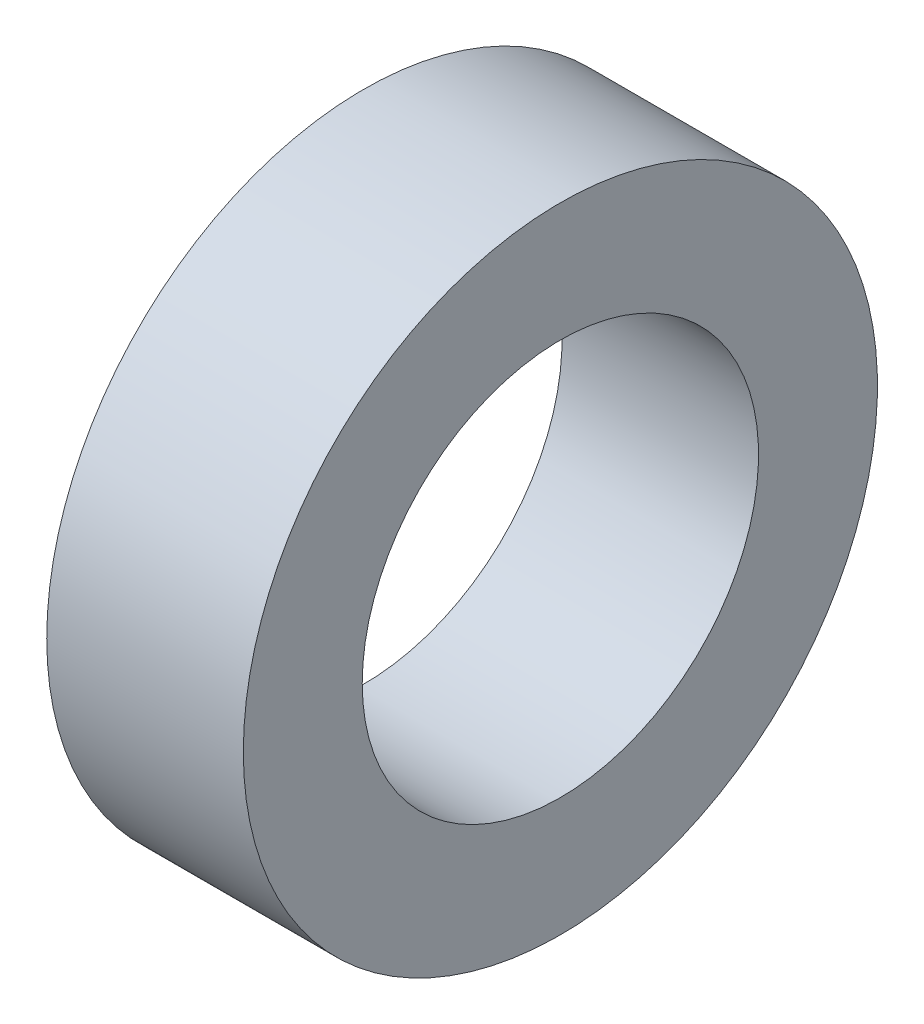
SolidWorks part; units mm, degrees
ref_plane "Front Plane" through (0, 0, 0) normal (0, 0, 1) x (1, 0, 0)
ref_plane "Top Plane" through (0, 0, 0) normal (0, 1, 0) x (1, 0, 0)
ref_plane "Right Plane" through (0, 0, 0) normal (1, 0, 0) x (0, 0, -1)
sketch "Sketch2" plane through (0, 0, 0) normal (0, 0, 1) x (1, 0, 0)
  line L0 (0, 0) -> (58.591, 0) construction
  line L2 (0, 0) -> (18.4, 0)
  line L3 (0, 0) -> (0, 2.5)
  line L4 (0, 2.5) -> (18.4, 2.5)
  line L5 (18.4, 0) -> (18.4, 2.5)
  line L6 (6, 2.5) -> (6, 6)
  line L11 (6, 6) -> (9.97, 6)
  line L16 (12.97, 6) -> (12.97, 3)
  line L17 (12.97, 3) -> (13.6304, 3)
  line L18 (13.6304, 3) -> (13.6304, 2.5)
  line L19 (13.6304, 2.5) -> (6, 2.5)
  line L22 (13.6304, 2.5) -> (16.1104, 2.5)
  line L23 (13.6304, 2.5) -> (13.6304, 4)
  line L24 (13.6304, 4) -> (16.1104, 4)
  line L25 (16.1104, 2.5) -> (16.1104, 4)
  line L27 (6, 6) -> (9.97, 6)
  line L28 (6, 6) -> (6, 9)
  line L29 (6, 9) -> (9.97, 9)
  line L30 (9.97, 6) -> (9.97, 9)
  line L31 (6, 9) -> (6, 8.25)
  line L32 (6, 8.25) -> (5, 8.25)
  line L33 (8.58, 22.001) -> (8.58, 12.476) construction
  line L34 (5, 12.476) -> (12.16, 12.476)
  line L35 (9.97, 9) -> (12.16, 9)
  line L36 (5, 7.5) -> (3, 7.5)
  line L37 (5, 8.25) -> (5, 12.476)
  line L38 (5, 7.5) -> (5, 14)
  line L39 (5, 14) -> (3, 14)
  line L40 (3, 7.5) -> (3, 14)
  line L41 (5, 22.001) -> (12.16, 22.001)
  line L42 (5, 22.001) -> (5, 30.1625)
  line L43 (5, 30.1625) -> (12.16, 30.1625)
  line L44 (12.16, 22.001) -> (12.16, 30.1625)
  line L49 (16.6304, 22.001) -> (16.6304, 7.5)
  line L51 (23.0104, 7.5) -> (23.0104, 6.5)
  line L54 (16.1104, 4) -> (13.6304, 4)
  line L56 (18.0304, 7.5) -> (23.0104, 7.5)
  line L57 (13.16, 22.001) -> (16.6304, 22.001)
  line L58 (16.1104, 3.5) -> (20.0104, 3.5)
  line L59 (29.9004, 14) -> (26.9004, 11)
  line L60 (4, 31.75) -> (18.0304, 31.75)
  line L61 (18.0304, 7.5) -> (23.0104, 7.5)
  line L62 (18.0304, 7.5) -> (18.0304, 12)
  line L63 (18.0304, 12) -> (23.0104, 12)
  line L64 (23.0104, 7.5) -> (23.0104, 12)
  line L65 (18.0304, 31.75) -> (18.0304, 12)
  line L66 (23.0104, 11) -> (26.9004, 11)
  line L67 (34.8004, 23) -> (31.3004, 19.5)
  line L68 (35.8004, 31) -> (38.7904, 33.99)
  line L69 (29.9004, 14) -> (29.9004, 15)
  line L70 (29.9004, 15) -> (22.9304, 15)
  line L71 (22.9304, 15) -> (21.0304, 15)
  line L72 (18.0304, 7.5) -> (16.6304, 7.5)
  line L73 (21.0304, 15) -> (21.0304, 43)
  line L74 (20.0304, 40) -> (10.0704, 40)
  line L75 (10.0704, 40) -> (4, 40)
  line L76 (21.0304, 43) -> (20.0304, 43)
  line L77 (22.9304, 15) -> (29.9004, 15)
  line L78 (22.9304, 15) -> (22.9304, 21)
  line L79 (22.9304, 21) -> (29.9004, 21)
  line L80 (29.9004, 15) -> (29.9004, 21)
  line L81 (10.0704, 40) -> (20.0304, 40)
  line L82 (10.0704, 40) -> (10.0704, 50)
  line L83 (10.0704, 50) -> (20.0304, 50)
  line L84 (20.0304, 40) -> (20.0304, 50)
  line L85 (4, 40) -> (4, 31.75)
  line L86 (12.97, 3) -> (12.97, 2.5)
  line L87 (31.3004, 19.5) -> (29.9004, 19.5)
  line L88 (21.51, 63.5) -> (21.51, 44)
  line L89 (21.51, 63.5) -> (25.9304, 63.5)
  line L90 (25.9304, 63.5) -> (25.9304, 25)
  line L91 (27.8304, 25) -> (25.9304, 25)
  line L92 (10.0704, 48) -> (9, 48)
  line L93 (9, 48) -> (9, 53.476)
  line L94 (9, 53.476) -> (20.0304, 53.476)
  line L95 (20.0304, 53.476) -> (20.0304, 50)
  line L96 (14.5152, 63.001) -> (14.5152, 53.476) construction
  line L97 (9, 63.001) -> (20.0304, 63.001)
  line L98 (9, 63.001) -> (9, 68.2625)
  line L99 (9, 68.2625) -> (20.0304, 68.2625)
  line L100 (20.0304, 63.001) -> (20.0304, 68.2625)
  line L101 (12.97, 6) -> (11.97, 6)
  line L102 (9, 42.5) -> (5, 42.5)
  line L103 (9, 42.5) -> (9, 55)
  line L104 (9, 55) -> (5, 55)
  line L105 (5, 42.5) -> (5, 55)
  line L106 (9.97, 6) -> (10.87, 6)
  line L107 (27.8304, 25) -> (34.8004, 25)
  line L108 (34.8004, 25) -> (34.8004, 23)
  line L109 (0, 0) -> (-2, 0)
  line L110 (0, 0) -> (0, 11)
  line L111 (27.8304, 25) -> (34.8004, 25)
  line L112 (27.8304, 25) -> (27.8304, 32.5)
  line L113 (27.8304, 32.5) -> (34.8004, 32.5)
  line L114 (34.8004, 25) -> (34.8004, 32.5)
  line L115 (35.8004, 31) -> (34.8004, 31)
  line L116 (27.8304, 32.5) -> (27.8304, 64.5)
  line L117 (21.1827, 74.025) -> (6.8477, 74.025)
  line L118 (6.8477, 74.025) -> (6.8477, 76.2)
  line L119 (38.7904, 47.29) -> (30.8304, 55.25)
  line L120 (0, 11) -> (-2, 11)
  line L121 (38.7904, 43.815) -> (30.8529, 43.815)
  line L123 (-4.8, 69.85) -> (1.55, 76.2)
  line L124 (38.7904, 47.29) -> (38.7904, 33.99)
  line L125 (-2, 0) -> (-2, 11)
  line L126 (38.7904, 37.465) -> (30.8529, 37.465)
  line L127 (30.8529, 43.815) -> (30.8529, 37.465)
  line L128 (6, 2.5) -> (6, 0)
  line L129 (0, 63.5) -> (0, 30)
  line L132 (5, 63.5) -> (0, 63.5)
  line L136 (-1.8, 30) -> (-11.76, 30)
  line L138 (-13.76, 25.4) -> (-2, 25.4)
  line L139 (-2, 25.4) -> (-2, 11.5)
  line L140 (27.8304, 64.5) -> (21.1827, 64.5)
  line L141 (-1.8, 30) -> (-11.76, 30)
  line L142 (-1.8, 30) -> (-1.8, 39)
  line L143 (-1.8, 39) -> (-11.76, 39)
  line L144 (-11.76, 30) -> (-11.76, 39)
  line L145 (21.1827, 64.5) -> (21.1827, 74.025)
  line L146 (-12.76, 37) -> (-12.76, 47.29)
  line L147 (-12.76, 37) -> (-11.76, 37)
  line L148 (30.8304, 55.25) -> (30.8304, 76.2)
  line L149 (11.97, 6) -> (11.97, 5.45)
  line L154 (-2, 11.5) -> (1, 11.5)
  line L155 (5, 60.6197) -> (24.05, 60.6197)
  line L160 (5, 60.6197) -> (5, 55.8572)
  line L161 (5, 55.8572) -> (24.05, 55.8572)
  line L166 (24.05, 60.6197) -> (24.05, 55.8572)
  line L167 (5, 60.6197) -> (24.05, 55.8572) construction
  line L172 (5, 55.8572) -> (24.05, 60.6197) construction
  line L173 (24.05, 62.2072) -> (25.9304, 62.2072)
  line L174 (11.97, 5.45) -> (10.87, 5.45)
  line L175 (10.87, 6) -> (10.87, 5.45)
  line L176 (24.05, 62.2072) -> (24.05, 54.2697)
  line L177 (24.05, 54.2697) -> (25.9304, 54.2697)
  line L178 (25.9304, 62.2072) -> (25.9304, 54.2697)
  line L179 (24.05, 62.2072) -> (25.9304, 54.2697) construction
  line L180 (24.05, 54.2697) -> (25.9304, 62.2072) construction
  line L181 (3, 19.6197) -> (15.7, 19.6197)
  line L182 (3, 19.6197) -> (3, 14.8572)
  line L183 (3, 14.8572) -> (15.7, 14.8572)
  line L184 (15.7, 19.6197) -> (15.7, 14.8572)
  line L185 (3, 19.6197) -> (15.7, 14.8572) construction
  line L186 (3, 14.8572) -> (15.7, 19.6197) construction
  line L187 (15.7, 21.2072) -> (16.6304, 21.2072)
  line L188 (15.7, 21.2072) -> (15.7, 13.2697)
  line L189 (15.7, 13.2697) -> (16.6304, 13.2697)
  line L190 (16.6304, 21.2072) -> (16.6304, 13.2697)
  line L191 (15.7, 21.2072) -> (16.6304, 13.2697) construction
  line L192 (15.7, 13.2697) -> (16.6304, 21.2072) construction
  line L193 (1, 11.5) -> (1, 6.5)
  line L194 (1, 6.5) -> (3, 6.5)
  line L195 (23.0104, 6.5) -> (20.0104, 3.5)
  line L196 (5, 63.5) -> (5, 42.5)
  line L197 (5, 42.5) -> (3, 42.5)
  line L198 (3, 42.5) -> (3, 6.5)
  line L199 (6, 0) -> (12.97, 0)
  line L200 (12.97, 0) -> (12.97, 2.5)
  line L201 (18.0304, 31.75) -> (18.0304, 35.875)
  line L202 (18.0304, 35.875) -> (21.0304, 35.875)
  line L203 (30.8304, 76.2) -> (6.8477, 76.2)
  line L204 (3.4027, 69.85) -> (7.8477, 69.85) construction
  line L205 (7.8477, 67.4687) -> (26.8977, 67.4688)
  line L206 (7.8477, 74.025) -> (7.8477, 64.5)
  line L207 (7.8477, 64.5) -> (-1.8, 64.5)
  line L208 (-1.8, 64.5) -> (-1.8, 39)
  line L209 (-12.76, 47.29) -> (-4.8, 55.25)
  line L210 (-4.8, 55.25) -> (-4.8, 69.85)
  line L211 (7.8477, 67.4687) -> (7.8477, 72.2313)
  line L212 (7.8477, 72.2313) -> (26.8977, 72.2313)
  line L213 (26.8977, 67.4688) -> (26.8977, 72.2313)
  line L214 (26.8977, 73.8187) -> (30.8304, 73.8187)
  line L215 (26.8977, 73.8187) -> (26.8977, 65.8813)
  line L216 (26.8977, 65.8813) -> (30.8304, 65.8813)
  line L217 (30.8304, 73.8187) -> (30.8304, 65.8813)
  line L218 (3.4027, 72.2313) -> (25.6277, 72.2313)
  line L219 (3.4027, 72.2313) -> (3.4027, 67.4687)
  line L220 (3.4027, 67.4687) -> (25.6277, 67.4687)
  line L221 (25.6277, 72.2313) -> (25.6277, 67.4687)
  line L222 (25.6277, 69.85) -> (21.1827, 69.85) construction
  line L223 (21.51, 44) -> (22.9304, 44)
  line L224 (22.9304, 44) -> (22.9304, 21)
  line L225 (13.6304, 4) -> (13.6304, 12.2697)
  line L226 (13.6304, 12.2697) -> (13.16, 12.2697)
  line L227 (13.16, 12.2697) -> (13.16, 22.001)
  line L228 (12.16, 9) -> (12.16, 12.476)
  line L229 (-1.8, 30) -> (0, 30)
  line L230 (9, 65.6317) -> (3.4027, 65.6317) construction
  line L231 (20.0304, 65.6317) -> (25.6277, 65.6317) construction
  line L232 (1.55, 76.2) -> (6.8477, 76.2)
  line L233 (-11.76, 30) -> (-13.76, 30)
  line L234 (-13.76, 30) -> (-13.76, 25.4)
  circle A0 centre (26.8804, 25.95) radius 0.95
  circle A1 centre (21.9804, 15.95) radius 0.95
  circle A2 centre (17.3304, 8.2) radius 0.7
  circle A3 centre (10.42, 6.45) radius 0.45
  circle A4 centre (-0.9, 30.9) radius 0.9
  point P7 (24.9902, 58.2385)
  point P131 (16.1652, 17.2385)
  point P135 (14.525, 58.2385)
  point P146 (9.35, 17.2385)
sketch "Sketch3" plane through (0, 0, 0) normal (0, 0, 1) x (1, 0, 0)
  line L0 (0, 2.5) -> (18.4, 2.5) construction
  line L1 (16.1104, 2.5) -> (16.1104, 4) construction
  line L2 (13.6304, 4) -> (16.1104, 4) construction
  line L3 (13.6304, 2.5) -> (13.6304, 4) construction
  line L4 (13.6304, 2.5) -> (16.1104, 2.5)
  line L5 (16.1104, 2.5) -> (16.1104, 4)
  line L6 (13.6304, 4) -> (16.1104, 4)
  line L7 (13.6304, 2.5) -> (13.6304, 4)
revolve "Revolve1" add sketch "Sketch3" angle 360 about L0
